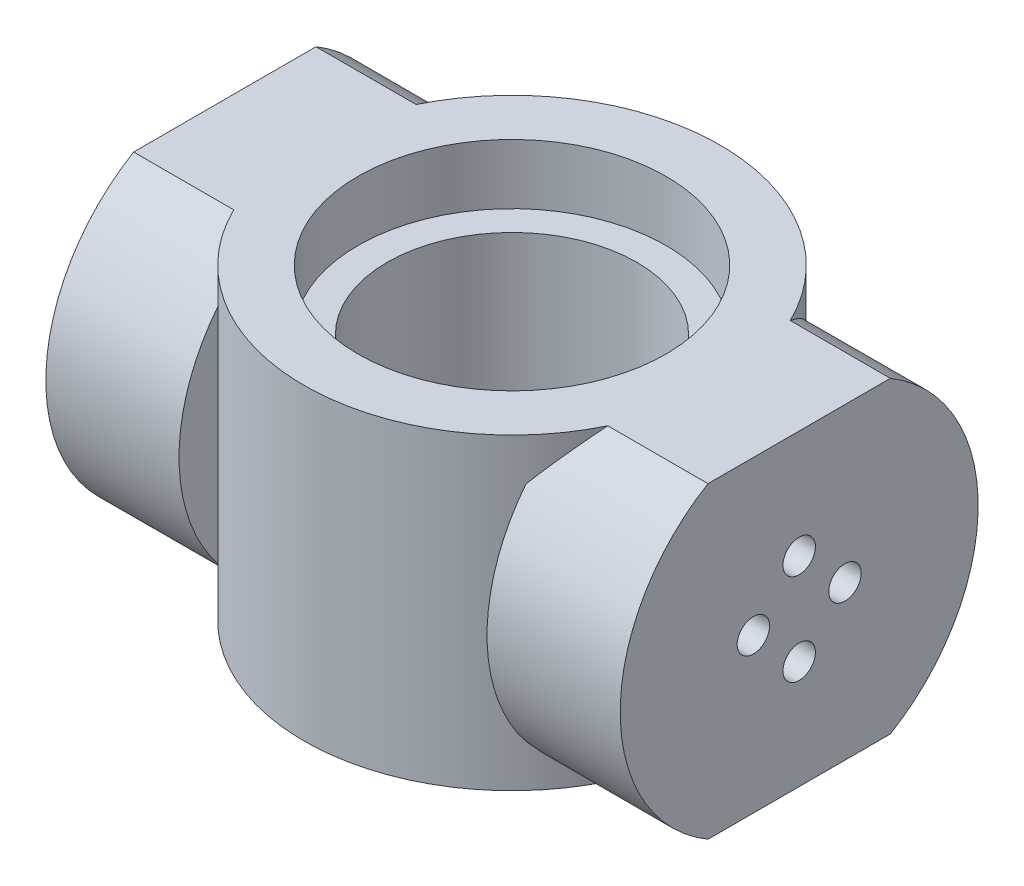
SolidWorks part; units mm, degrees
ref_plane "Ebene vorne" through (0, 0, 0) normal (0, 0, 1) x (1, 0, 0)
ref_plane "Ebene oben" through (0, 0, 0) normal (0, 1, 0) x (1, 0, 0)
ref_plane "Ebene rechts" through (0, 0, 0) normal (1, 0, 0) x (0, 0, -1)
ref_plane "Ebene1" through (18.5, 0, 0) normal (1, 0, 0) x (0, 0, -1)
sketch "Skizze1" plane through (0, 0, 0) normal (0, 1, 0) x (1, 0, 0)
  circle A0 centre (0, 0) radius 25
  circle A1 centre (0, 0) radius 18.5
  dimension "D1" = 50
  dimension "D2" = 37
extrude "Aufsatz-Linear austragen1" add sketch "Skizze1" along normal mid plane 37
sketch "Skizze2" plane through (0, 0, 0) normal (0, 1, 0) x (1, 0, 0)
  circle A0 centre (0, 0) radius 15
  circle A5 centre (0, 0) radius 18.5
  circle A6 centre (0, 0) radius 18.5 construction
  dimension "D2" = 30
extrude "Aufsatz-Linear austragen2" add sketch "Skizze2" along normal mid plane 22.6
sketch "Skizze3" plane through (18.5, 0, 0) normal (1, 0, 0) x (0, 0, -1)
  line L9 (-25, -18.5) -> (25, -18.5) construction
  circle A2 centre (0, 0) radius 21.5
  dimension "D1" = 3
extrude "Aufsatz-Linear austragen3" add sketch "Skizze3" along normal blind 16
sketch "Skizze4" plane through (34.5, 0, 0) normal (1, 0, 0) x (0, 0, -1)
  line L0 (0, 0) -> (-5.5, 0) construction
  circle A0 centre (-5.5, 0) radius 1.95
  circle A1 centre (0, 5.5) radius 1.95
  circle A2 centre (5.5, 0) radius 1.95
  circle A3 centre (0, -5.5) radius 1.95
  point P13 (0, 0)
  dimension "D2" = 3.9
  dimension "D1" = 5.5
  dimension "D3" = 4
extrude "Schnitt-Linear austragen1" cut sketch "Skizze4" against normal blind 4.2
mirror "Spiegeln1" about plane through (0, 0, 0) normal (1, 0, 0) of "Schnitt-Linear austragen1", "Aufsatz-Linear austragen3"
sketch "Skizze5" plane through (0, 29.286, 0) normal (-1, 0, 0) x (0, -1, 0)
  line L1 (10.786, 25) -> (47.786, 25)
  line L2 (10.786, 25) -> (10.786, -25)
  line L3 (10.786, -25) -> (47.786, -25)
  line L4 (47.786, 25) -> (47.786, -25)
  line L5 (47.786, 25) -> (10.786, 25) construction
  line L6 (10.786, 25) -> (10.786, 10.9545) construction
extrude "Schnitt-Linear austragen2" cut sketch "Skizze5" against normal through all both and the other way through all flip side to cut
ref_axis "Achse1" through (31.35, 0, 0) along (-1, 0, 0)
ref_axis "Achse2" through (0, -20.35, 0) along (0, 1, 0)
